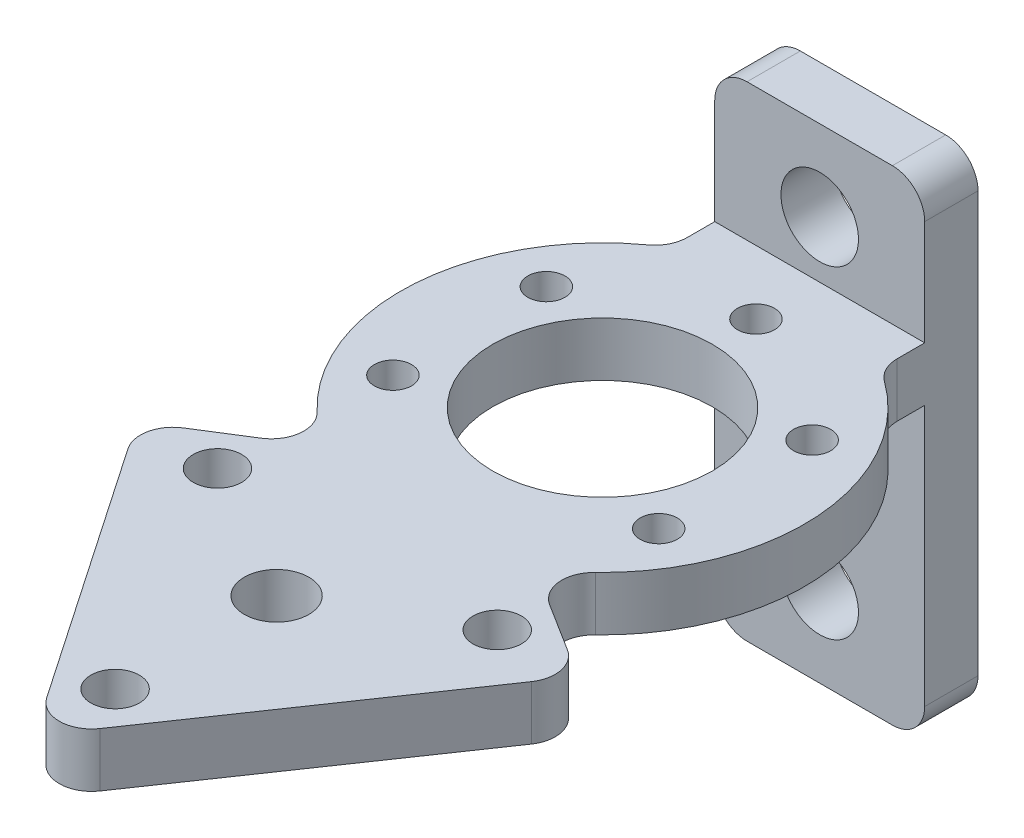
SolidWorks part; units mm, degrees
material "PLA"
ref_plane "Plan de face" through (0, 0, 0) normal (0, 0, 1) x (1, 0, 0)
ref_plane "Plan de dessus" through (0, 0, 0) normal (0, 1, 0) x (1, 0, 0)
ref_plane "Plan de droite" through (0, 0, 0) normal (1, 0, 0) x (0, 0, -1)
sketch "Esquisse1" plane through (0, 0, 0) normal (0, 0, 1) x (1, 0, 0)
  line L0 (55, 0) -> (-55, 0) construction
  line L1 (-6.5, -15) -> (6.5, -15)
  line L2 (-6.5, -15) -> (-6.5, 15)
  line L3 (-6.5, 15) -> (6.5, 15)
  line L4 (6.5, -15) -> (6.5, 15)
  line L5 (-6.5, -15) -> (6.5, 15) construction
  line L6 (-6.5, 15) -> (6.5, -15) construction
  circle A0 centre (0, 10) radius 2.4
  circle A1 centre (0, -10) radius 2.4
  point P0 (0, 0)
  point P8 (0, 0)
  dimension "D4" = 4.8
  dimension "D1" = 30
  dimension "D2" = 13
  dimension "D3" = 10
extrude "Boss.-Extru.1" add sketch "Esquisse1" along normal blind 3.3
fillet "Congé1" radius 2 4 edges at (6.5, -15, 1.65) (-6.5, -15, 1.65) (6.5, 15, 1.65) (-6.5, 15, 1.65)
sketch "Esquisse2" plane through (0, 0, 3.3) normal (0, 0, 1) x (1, 0, 0)
  line L0 (6.5, -13) -> (6.5, 13) construction
  line L3 (-6.5, 6.5) -> (6.5, 6.5)
  line L5 (-6.5, 13) -> (-6.5, -13) construction
  line L7 (-6.5, 6.5) -> (-6.5, 3.15)
  line L10 (-6.5, 3.15) -> (6.5, 3.15)
  line L14 (6.5, 6.5) -> (6.5, 3.15)
  point P0 (0, 0)
  point P8 (0, 0)
  dimension "D1" = 3.15
  dimension "D3" = 3.35
extrude "Boss.-Extru.2" add sketch "Esquisse2" along normal blind 2.77
sketch "Esquisse4" plane through (0, 6.5, 0) normal (0, 1, 0) x (1, 0, 0)
  line L1 (-6.5, -6.07) -> (6.5, -6.07)
  line L3 (-6.5, -27.4242) -> (6.5, -27.4242)
  circle A4 centre (0, -16.7471) radius 6.8
  arc A5 (-6.5, -6.07) -> (-6.5, -27.4242) centre (0, -16.7471) ccw
  arc A6 (6.5, -27.4242) -> (6.5, -6.07) centre (0, -16.7471) ccw
  point P9 (0, 0)
  point P25 (0, -16.7471)
  point P28 (0, -16.7471)
  dimension "D2" = 12.5
  dimension "D3" = 13
  dimension "D6" = 6.8
  dimension "D1" = 12.5
extrude "Boss.-Extru.4" add sketch "Esquisse4" against normal up to surface (3.35 mm away) up to face at (0, 3.15, 4.685)
sketch "Esquisse6" plane through (0, 6.5, 0) normal (0, 1, 0) x (1, 0, 0)
  line L2 (0, -16.7471) -> (8.2272, -11.9971) construction
  line L3 (0, -16.7471) -> (-8.2272, -11.9971) construction
  line L4 (0, -16.7471) -> (0, -7.2471) construction
  line L5 (0, -16.7471) -> (-8.2272, -21.4971) construction
  line L6 (0, -16.7471) -> (0, -26.2471) construction
  line L7 (0, -16.7471) -> (8.2272, -21.4971) construction
  circle A0 centre (0, -7.2471) radius 1.15
  circle A1 centre (-8.2272, -11.9971) radius 1.15
  circle A2 centre (8.2272, -11.9971) radius 1.15
  circle A3 centre (-8.2272, -21.4971) radius 1.15
  circle A7 centre (8.2272, -21.4971) radius 1.15
  dimension "D2" = 2.3
  dimension "D5" = 2.3
  dimension "D6" = 2.3
  dimension "D7" = 9.5
  dimension "D14" = 2.3
  dimension "D15" = 2.3
  dimension "D1" = 9.5
  dimension "D3" = 60
  dimension "D4" = 60
  dimension "D8" = 9.5
  dimension "D9" = 60
  dimension "D10" = 60
  dimension "D11" = 9.5
  dimension "D12" = 9.5
  dimension "D13" = 9.5
extrude "Enlèv. mat.-Extru.2" cut sketch "Esquisse6" against normal through all
sketch "Esquisse8" plane through (0, 6.5, 0) normal (0, 1, 0) x (1, 0, 0)
  line L6 (-6.5, -27.4242) -> (6.5, -27.4242) construction
  line L7 (6.5, -27.4242) -> (-6.5, -27.4242)
  line L8 (0, -9.9471) -> (0, -23.5471) construction
  line L9 (0, -36.9271) -> (0, -27.4242) construction
  line L10 (0, -36.9271) -> (8.6603, -31.9271) construction
  line L11 (0, -36.9271) -> (-8.6603, -31.9271) construction
  line L12 (-6.5, -27.4242) -> (-13.6603, -31.9271)
  line L13 (-13.6603, -31.9271) -> (0, -51.9271)
  line L14 (0, -51.9271) -> (13.6603, -31.9271)
  line L15 (13.6603, -31.9271) -> (6.5, -27.4242)
  circle A0 centre (0, -36.9271) radius 2
  circle A1 centre (0, -36.9271) radius 10 construction
  circle A2 centre (8.6603, -31.9271) radius 1.5
  circle A3 centre (0, -16.7471) radius 6.8 construction
  circle A4 centre (-8.6603, -31.9271) radius 1.5
  circle A7 centre (0, -46.9271) radius 1.5
  point P16 (0, -16.7471)
  dimension "D2" = 4
  dimension "D5" = 3
  dimension "D6" = 3
  dimension "D7" = 3
  dimension "D1" = 20.18
  dimension "D3" = 120
  dimension "D4" = 60
  dimension "D8" = 5
  dimension "D9" = 5
  dimension "D10" = 5
  dimension "D11" = 8.6603
extrude "Boss.-Extru.5" add sketch "Esquisse8" against normal up to surface (3.35 mm away) up to face at (0, 3.15, 8.3971)
fillet "Congé2" radius 2 7 edges at (13.6603, 4.825, 31.9271) (0, 4.825, 51.9271) (-13.6603, 4.825, 31.9271) (-6.5, 4.825, 27.4242) (6.5, 4.825, 27.4242) (6.5, 4.825, 6.07) (-6.5, 4.825, 6.07)
